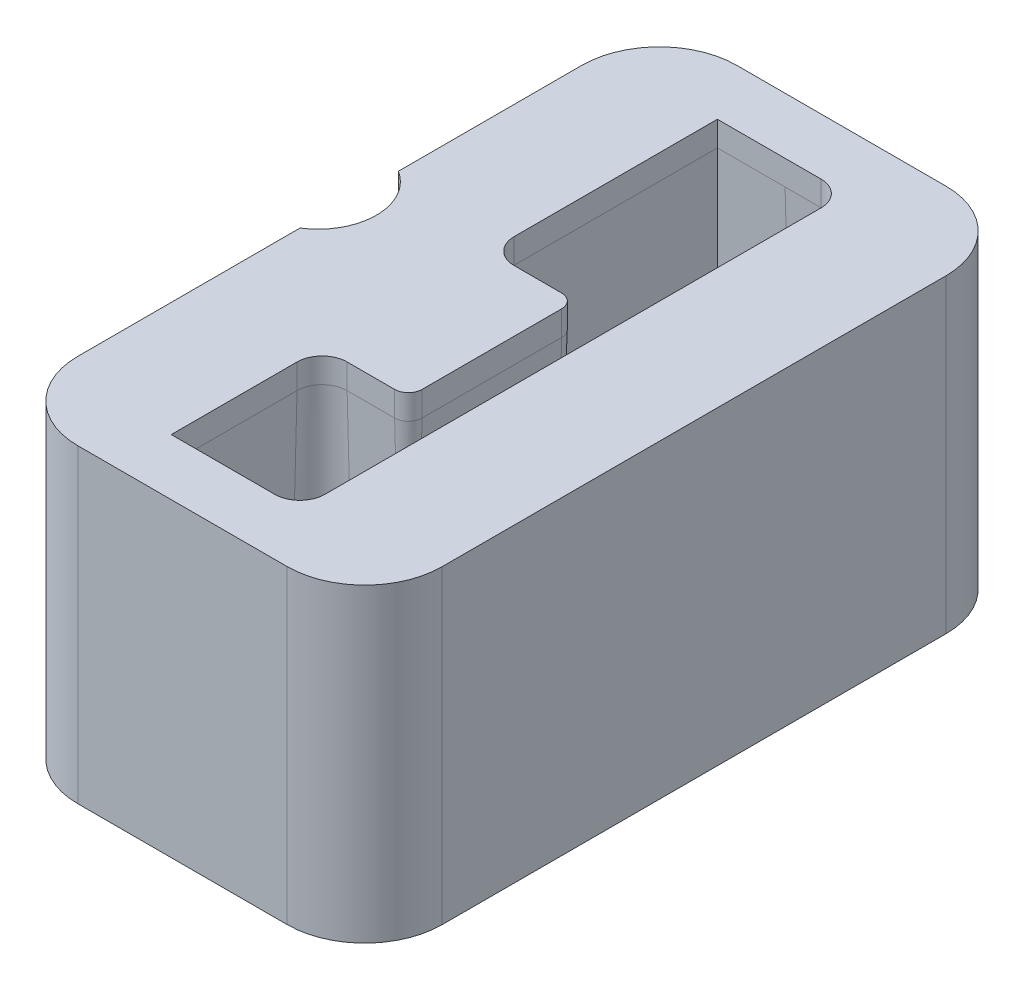
SolidWorks part; units mm, degrees
material "K110"
ref_plane "Front Plane" through (0, 0, 0) normal (0, 0, 1) x (1, 0, 0)
ref_plane "Top Plane" through (0, 0, 0) normal (0, 1, 0) x (1, 0, 0)
ref_plane "Right Plane" through (0, 0, 0) normal (1, 0, 0) x (0, 0, -1)
sketch "Sketch1" plane through (0, 0, 0) normal (0, 1, 0) x (1, 0, 0)
  line L1 (-23.5, -42.5) -> (23.5, -42.5)
  line L2 (-23.5, -42.5) -> (-23.5, 42.5)
  line L3 (-23.5, 42.5) -> (23.5, 42.5)
  line L4 (23.5, -42.5) -> (23.5, 42.5)
  line L5 (-23.5, -42.5) -> (23.5, 42.5) construction
  line L6 (-23.5, 42.5) -> (23.5, -42.5) construction
  point P0 (0, 0)
  dimension "D1" = 85
  dimension "D2" = 47
extrude "Boss-Extrude1" add sketch "Sketch1" against normal blind 40
fillet "Fillet1" radius 10 4 edges at (-23.5, -20, -42.5) (23.5, -20, -42.5) (-23.5, -20, 42.5) (23.5, -20, 42.5)
sketch "Sketch3" plane through (0, 0, 0) normal (0, 1, 0) x (1, 0, 0)
  line L88 (4.63, 35.23) -> (-8.73, 35.23)
  line L89 (-8.73, 35.23) -> (-8.73, 9)
  line L90 (-5.5, 5.77) -> (0.63, 5.77)
  line L91 (2.4, 4) -> (2.4, -14)
  line L92 (0.63, -15.77) -> (-5.5, -15.77)
  line L93 (-8.73, -19) -> (-8.73, -35.23)
  line L94 (-8.73, -35.23) -> (4.63, -35.23)
  line L95 (7.86, -32) -> (7.86, 32)
  line L96 (4.63, 35.23) -> (-8.73, 35.23)
  line L97 (-8.73, 35.23) -> (-8.73, 9)
  line L98 (-5.5, 5.77) -> (0.63, 5.77)
  line L99 (2.4, 4) -> (2.4, -14)
  line L100 (0.63, -15.77) -> (-5.5, -15.77)
  line L101 (-8.73, -19) -> (-8.73, -35.23)
  line L102 (-8.73, -35.23) -> (4.63, -35.23)
  line L103 (7.86, -32) -> (7.86, 32)
  arc A48 (7.86, 32) -> (4.63, 35.23) centre (4.63, 32) ccw
  arc A49 (-8.73, 9) -> (-5.5, 5.77) centre (-5.5, 9) ccw
  arc A50 (2.4, 4) -> (0.63, 5.77) centre (0.63, 4) ccw
  arc A51 (0.63, -15.77) -> (2.4, -14) centre (0.63, -14) ccw
  arc A52 (-5.5, -15.77) -> (-8.73, -19) centre (-5.5, -19) ccw
  arc A53 (4.63, -35.23) -> (7.86, -32) centre (4.63, -32) ccw
  arc A54 (7.86, 32) -> (4.63, 35.23) centre (4.63, 32) ccw
  arc A55 (-8.73, 9) -> (-5.5, 5.77) centre (-5.5, 9) ccw
  arc A56 (2.4, 4) -> (0.63, 5.77) centre (0.63, 4) ccw
  arc A57 (0.63, -15.77) -> (2.4, -14) centre (0.63, -14) ccw
  arc A58 (-5.5, -15.77) -> (-8.73, -19) centre (-5.5, -19) ccw
  arc A59 (4.63, -35.23) -> (7.86, -32) centre (4.63, -32) ccw
  dimension "D1" = 0.23
extrude "Cut-Extrude1" cut sketch "Sketch3" against normal up to next
sketch "Sketch4" plane through (0, 0, 0) normal (1, 0, 0) x (0, 0, -1)
  line L6 (35.23, -3.2) -> (36.1936, -40)
  line L7 (35.23, -40) -> (35.23, 0) construction
  line L9 (36.1936, -40) -> (35.23, -40)
  line L10 (35.23, -40) -> (35.23, -3.2)
  line L11 (25.85, 0) -> (-25.85, 0) construction
  dimension "D1" = 3.2
  dimension "D2" = 1.5
sketch "Sketch5" plane through (0, 0, 0) normal (0, 1, 0) x (1, 0, 0)
  line L16 (-8.73, -35.23) -> (4.63, -35.23) construction
  line L17 (-8.73, -19) -> (-8.73, -35.23) construction
  line L18 (0.63, -15.77) -> (-5.5, -15.77) construction
  line L19 (2.4, 4) -> (2.4, -14) construction
  line L20 (-5.5, 5.77) -> (0.63, 5.77) construction
  line L21 (-8.73, 35.23) -> (-8.73, 9) construction
  line L22 (4.63, 35.23) -> (-8.73, 35.23) construction
  line L23 (7.86, -32) -> (7.86, 32) construction
  line L24 (-8.73, -35.23) -> (4.63, -35.23)
  line L25 (-8.73, -19) -> (-8.73, -35.23)
  line L26 (0.63, -15.77) -> (-5.5, -15.77)
  line L27 (2.4, 4) -> (2.4, -14)
  line L28 (-5.5, 5.77) -> (0.63, 5.77)
  line L29 (-8.73, 35.23) -> (-8.73, 9)
  line L30 (4.63, 35.23) -> (-8.73, 35.23)
  line L31 (7.86, -32) -> (7.86, 32)
  arc A8 (4.63, -35.23) -> (7.86, -32) centre (4.63, -32) ccw construction
  arc A9 (-5.5, -15.77) -> (-8.73, -19) centre (-5.5, -19) ccw construction
  arc A10 (0.63, -15.77) -> (2.4, -14) centre (0.63, -14) ccw construction
  arc A11 (2.4, 4) -> (0.63, 5.77) centre (0.63, 4) ccw construction
  arc A12 (-8.73, 9) -> (-5.5, 5.77) centre (-5.5, 9) ccw construction
  arc A13 (7.86, 32) -> (4.63, 35.23) centre (4.63, 32) ccw construction
  arc A14 (4.63, -35.23) -> (7.86, -32) centre (4.63, -32) ccw
  arc A15 (-5.5, -15.77) -> (-8.73, -19) centre (-5.5, -19) ccw
  arc A16 (0.63, -15.77) -> (2.4, -14) centre (0.63, -14) ccw
  arc A17 (2.4, 4) -> (0.63, 5.77) centre (0.63, 4) ccw
  arc A18 (-8.73, 9) -> (-5.5, 5.77) centre (-5.5, 9) ccw
  arc A19 (7.86, 32) -> (4.63, 35.23) centre (4.63, 32) ccw
sweep "Cut-Sweep1" cut profiles "Sketch4" path "Sketch5"
hole_wizard "M6 Tapped Hole1" positions "Sketch8" profile "Sketch7" tap size "M6" standard "ISO"
sketch "Sketch8" plane through (0, -40, 0) normal (0, -1, 0) x (-1, 0, 0)
  line L0 (-13.5, 42.5) -> (13.5, 42.5) construction
  line L1 (-23.5, -32.5) -> (-23.5, 32.5) construction
  line L2 (23.5, 32.5) -> (23.5, -32.5) construction
  line L3 (13.5, -42.5) -> (-13.5, -42.5) construction
  point P0 (-16.5, 35.5)
  point P2 (16.5, 35.5)
  point P4 (16.5, -35.5)
  point P6 (-16.5, -35.5)
  dimension "D1" = 7
  dimension "D2" = 7
  dimension "D3" = 7
  dimension "D4" = 7
sketch "Sketch7" plane through (16.5, -40, -35.5) normal (1, 0, 0) x (0, 0, -1)
  line L0 (0, 0) -> (0, 18.5022)
  line L1 (0, 18.5022) -> (2.5, 17)
  line L2 (2.5, 17) -> (2.5, 0.525)
  line L3 (2.5, 0.525) -> (3.025, 0)
  line L5 (3.025, 0) -> (0, 0)
  line L6 (-2.5, 0.525) -> (-3.025, 0) construction
  line L10 (0, 18.5022) -> (-2.5, 17) construction
  line L11 (0, -6.35) -> (0, 107.95) construction
  dimension "Tap Drill Dia." = 5
  dimension "Tap Drill Depth" = 17
  dimension "Near C'Sink Dia." = 6.05
  dimension "Near C'Sink Angle" = 90
  dimension "Drill Angle" = 118
cosmetic thread "Hole Thread1" parameters "D1"=12, "D2"=6
cosmetic thread "Hole Thread2" parameters "D1"=12, "D2"=6
cosmetic thread "Hole Thread3" parameters "D1"=12, "D2"=6
cosmetic thread "Hole Thread4" parameters "D1"=12, "D2"=6
extrude "Cut-Extrude2" cut sketch "Sketch9" against normal through all
sketch "Sketch9" plane through (236.38, 0, 7.73) normal (0, 1, 0) x (1, 0, 0)
  circle A0 centre (-263.88, 10.23) radius 7.5
